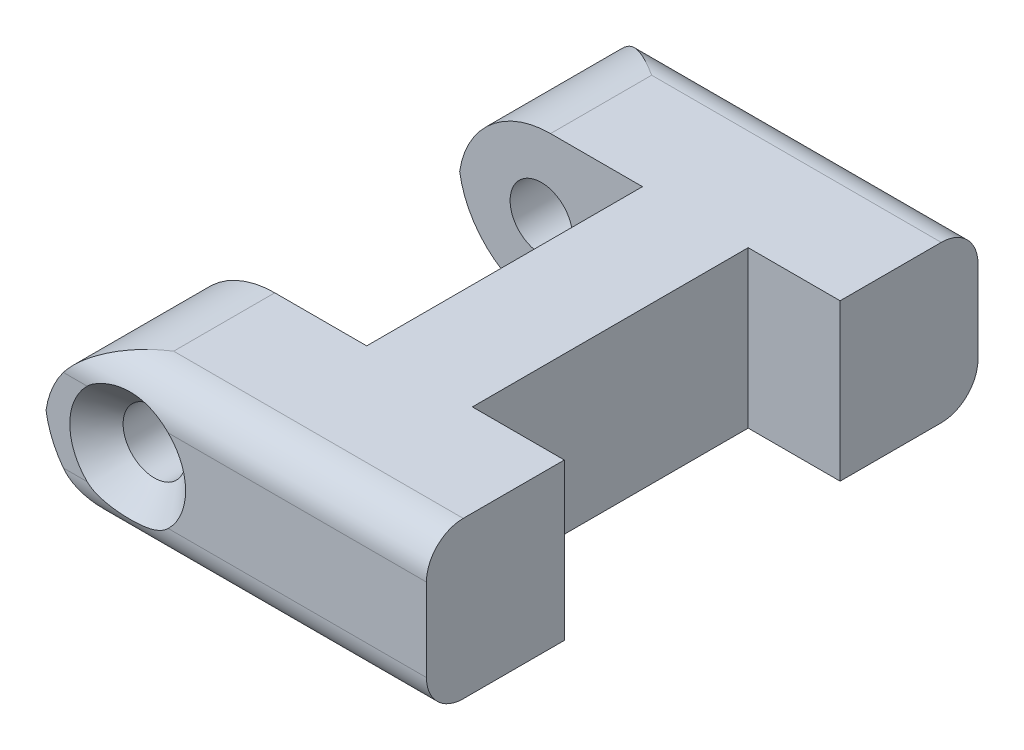
SolidWorks part; units mm, degrees
ref_plane "Front" through (0, 0, 0) normal (0, 0, 1) x (1, 0, 0)
ref_plane "Top" through (0, 0, 0) normal (0, 1, 0) x (1, 0, 0)
ref_plane "Right" through (0, 0, 0) normal (1, 0, 0) x (0, 0, -1)
sketch "Sketch1" plane through (0, 0, 0) normal (0, 1, 0) x (1, 0, 0)
  line L0 (-19.6186, 4.0533) -> (41.7606, 4.0533) construction
  line L1 (-11.532, 19.0533) -> (9.218, 19.0533)
  line L2 (-11.532, 19.0533) -> (-11.532, 11.5533)
  line L3 (-11.532, -10.9467) -> (9.218, -10.9467)
  line L4 (9.218, 19.0533) -> (9.218, 11.5533)
  line L5 (-11.532, -3.4467) -> (-11.532, -10.9467)
  line L6 (-11.532, 11.5533) -> (-1.532, 11.5533)
  line L7 (3.343, 28.9107) -> (3.343, -26.1199) construction
  line L8 (-11.532, -3.4467) -> (-1.532, -3.4467)
  line L9 (-1.532, 11.5533) -> (-1.532, -3.4467)
  line L10 (9.218, -3.4467) -> (4.218, -3.4467)
  line L11 (4.218, 11.5533) -> (4.218, -3.4467)
  line L12 (9.218, 11.5533) -> (4.218, 11.5533)
  line L13 (9.218, -3.4467) -> (9.218, -10.9467)
  point P16 (0, 0)
  point P17 (0, 0)
  point P18 (0, 0)
  point P19 (0, 0)
  dimension "D1" = 30
  dimension "D2" = 15
  dimension "D3" = 7.5
  dimension "D4" = 15
  dimension "D5" = 10
  dimension "D6" = 20.75
  dimension "D7" = 5
extrude "Boss-Extrude1" add sketch "Sketch1" along normal blind 8.5
sketch "Sketch2" plane through (0, 0, 10.9467) normal (0, 0, 1) x (1, 0, 0)
  line L0 (-7.032, 14.8176) -> (-7.032, -4.365) construction
  line L1 (-11.532, 8.5) -> (-11.532, 0) construction
  line L2 (-14.4304, 4.25) -> (2.4349, 4.25) construction
  line L3 (-11.532, 8.5) -> (9.218, 8.5) construction
  circle A0 centre (-7.032, 4.25) radius 1.5
  point P2 (-11.532, 4.25)
  dimension "D3" = 3
  dimension "D1" = 4.5
  dimension "D2" = 4.25
extrude "Cut-Extrude1" cut sketch "Sketch2" against normal up to surface (30 mm away) up to face at (-1.157, 4.25, -19.0533)
fillet "Fillet1" radius 5 4 edges at (-11.532, 0, -15.3033) (-11.532, 8.5, -15.3033) (-11.532, 0, 7.1967) (-11.532, 8.5, 7.1967)
fillet "Fillet2" radius 2 4 edges at (1.343, 8.5, -19.0533) (1.343, 8.5, 10.9467) (1.343, 0, -19.0533) (1.343, 0, 10.9467) tangent propagation no
hole_wizard "CSK for M3 Countersunk Flat Head Screw1" positions "Sketch4" profile "Sketch3" countersink size "M3" standard "ISO" end condition through all
sketch "Sketch4" plane through (0, 0, 10.9467) normal (0, 0, 1) x (1, 0, 0)
  point P0 (-7.032, 4.25)
sketch "Sketch3" plane through (-7.032, 4.25, 10.9467) normal (1, 0, 0) x (0, -1, 0)
  line L0 (0, 0) -> (0, 30)
  line L1 (0, 30) -> (1.7, 30)
  line L2 (1.7, 30) -> (1.7, 1.45)
  line L3 (1.7, 1.45) -> (3.15, 0)
  line L5 (3.15, 0) -> (0, 0)
  line L6 (-1.7, 1.45) -> (-3.15, 0) construction
  line L11 (0, -6.35) -> (0, 107.95) construction
  dimension "Thru Hole Dia." = 3.4
  dimension "Thru Hole Depth" = 30
  dimension "Near C'Sink Dia." = 6.3
  dimension "Near C'Sink Angle" = 90
sketch "Sketch5" plane through (0, 0, -19.0533) normal (0, 0, -1) x (-1, 0, 0)
  line L1 (7.032, 7.4254) -> (4.282, 5.8377)
  line L2 (4.282, 5.8377) -> (4.282, 2.6623)
  line L3 (4.282, 2.6623) -> (7.032, 1.0746)
  line L4 (7.032, 1.0746) -> (9.782, 2.6623)
  line L5 (9.782, 2.6623) -> (9.782, 5.8377)
  line L6 (9.782, 5.8377) -> (7.032, 7.4254)
  circle A0 centre (7.032, 4.25) radius 2.75 construction
  dimension "D1" = 5.5
extrude "Cut-Extrude2" cut sketch "Sketch5" against normal blind 3
